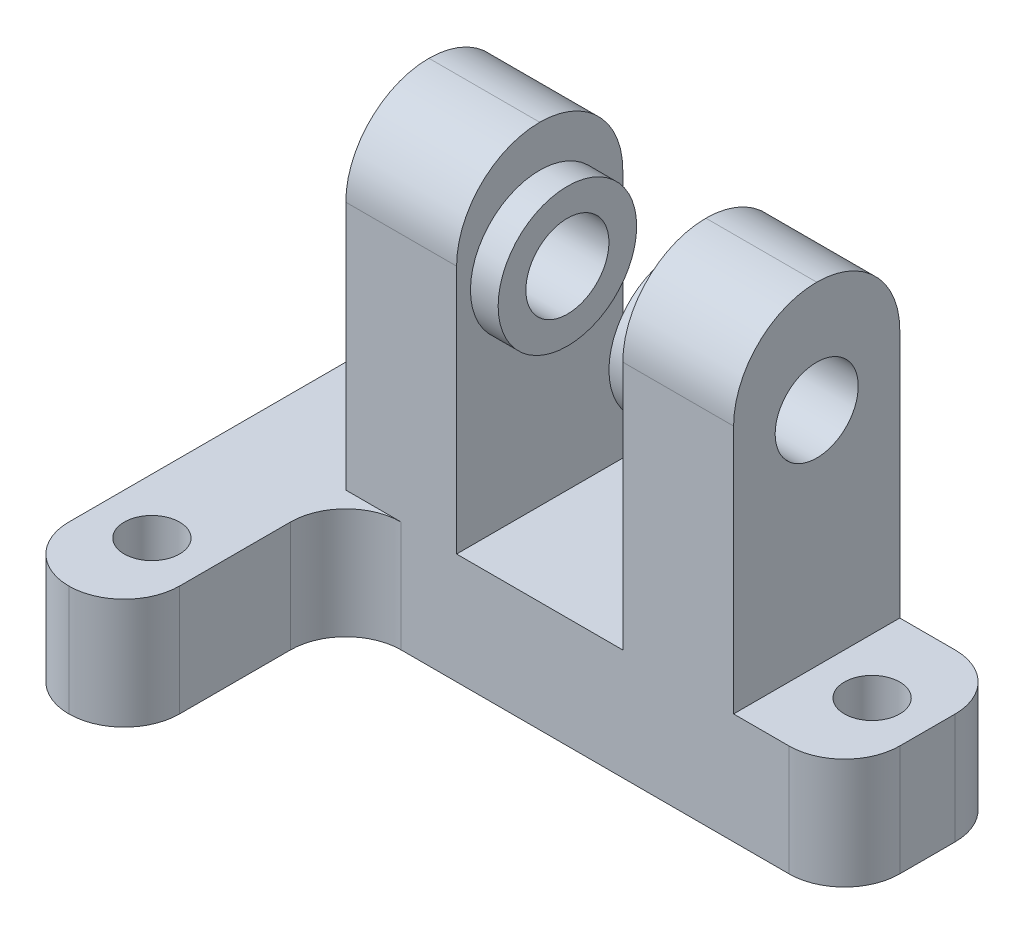
SolidWorks part; units mm, degrees
ref_plane "Front Plane" through (0, 0, 0) normal (0, 0, 1) x (1, 0, 0)
ref_plane "Top Plane" through (0, 0, 0) normal (0, 1, 0) x (1, 0, 0)
ref_plane "Right Plane" through (0, 0, 0) normal (1, 0, 0) x (0, 0, -1)
sketch "Sketch2" plane through (0, 0, 0) normal (0, 1, 0) x (1, 0, 0)
  line L1 (-7, 3) -> (7, 3)
  line L2 (-7, 3) -> (-7, -3)
  line L3 (-7, -3) -> (7, -3)
  line L4 (7, 3) -> (7, -3)
  line L5 (-7, 3) -> (7, -3) construction
  line L6 (-7, -3) -> (7, 3) construction
  point P0 (0, 0)
extrude "Boss-Extrude1" add sketch "Sketch2" along normal blind 4
sketch "Sketch3" plane through (0, 4, 0) normal (0, 1, 0) x (1, 0, 0)
  line L0 (-7, -3) -> (-3, -3)
  line L1 (-7, -3) -> (7, -3) construction
  line L2 (-3, -3) -> (-3, 3)
  line L3 (7, 3) -> (-7, 3) construction
  line L4 (-3, 3) -> (-7, 3)
  line L5 (-7, 3) -> (-7, -3)
  line L6 (7, -3) -> (3, -3)
  line L7 (3, -3) -> (3, 3)
  line L8 (3, 3) -> (7, 3)
  line L9 (7, 3) -> (7, -3)
extrude "Boss-Extrude2" add sketch "Sketch3" along normal blind 12
sketch "Sketch4" plane through (7, 0, 0) normal (1, 0, 0) x (0, 0, -1)
  circle A0 centre (0, 12) radius 1.5
extrude "Cut-Extrude1" cut sketch "Sketch4" against normal through all both and the other way through all
sketch "Sketch5" plane through (-3, 0, 0) normal (1, 0, 0) x (0, 0, -1)
  circle A0 centre (0, 12) radius 1.5
  circle A1 centre (0, 12) radius 2.5
extrude "Boss-Extrude3" add sketch "Sketch5" along normal blind 1
sketch "Sketch6" plane through (3, 0, 0) normal (-1, 0, 0) x (0, 0, 1)
  circle A0 centre (0, 12) radius 1.5
  circle A1 centre (0, 12) radius 2.5
extrude "Boss-Extrude4" add sketch "Sketch6" along normal blind 1
sketch "Sketch7" plane through (0, 4, 0) normal (0, 1, 0) x (1, 0, 0)
  line L2 (11, 3) -> (11, -3)
  line L4 (-7, -3) -> (-7, 3)
  line L5 (-7, 3) -> (-7, -3) construction
  line L6 (-7, 3) -> (-11, 3)
  line L7 (-11, 3) -> (-11, -3)
  line L9 (11, 3) -> (7, 3)
  line L10 (7, 3) -> (7, -3)
  line L14 (-11, -3) -> (-11, -11)
  line L15 (-11, -11) -> (-7, -11)
  line L16 (-7, -11) -> (-7, -3)
  line L17 (11, -3) -> (7, -3)
  circle A0 centre (9, 0) radius 1
  circle A1 centre (-9, -8) radius 1
extrude "Boss-Extrude5" add sketch "Sketch7" against normal blind 4
fillet "Fillet1" radius 2 6 edges at (-11, 2, -3) (11, 2, -3) (11, 2, 3) (-7, 2, 3) (-7, 2, 11) (-11, 2, 11)
fillet "Fillet2" radius 3 4 edges at (-5, 16, -3) (5, 16, -3) (5, 16, 3) (-5, 16, 3)
